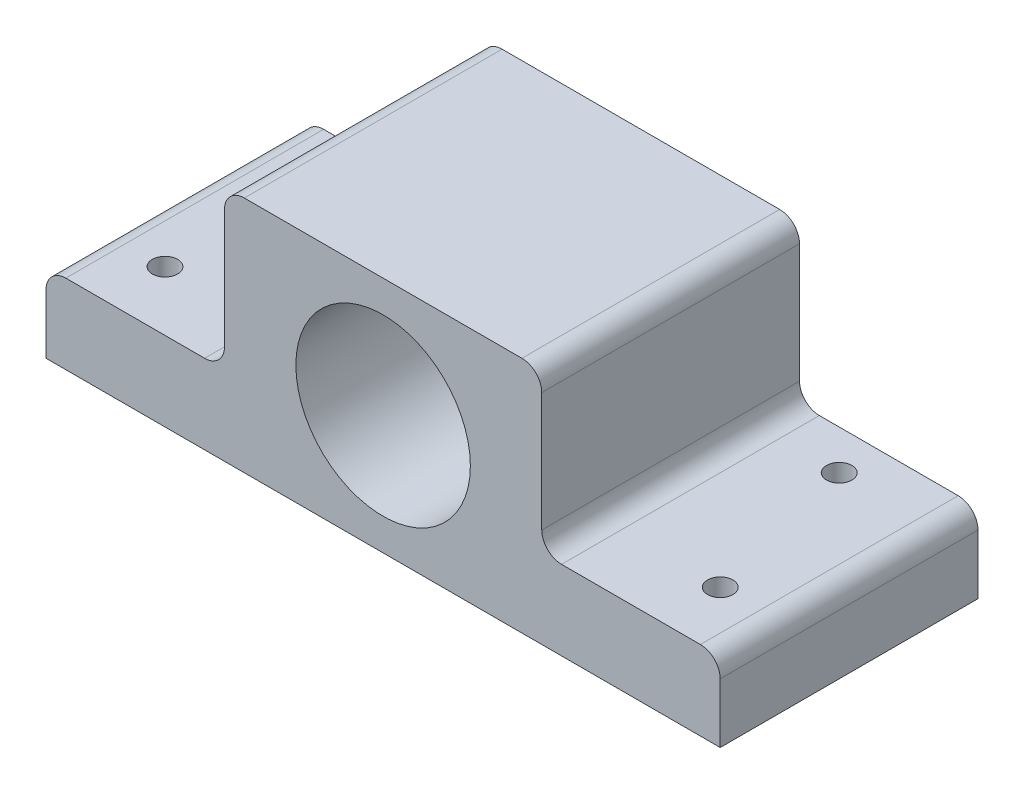
SolidWorks part; units mm, degrees
ref_plane "Front Plane" through (0, 0, 0) normal (0, 0, 1) x (1, 0, 0)
ref_plane "Top Plane" through (0, 0, 0) normal (0, 1, 0) x (1, 0, 0)
ref_plane "Right Plane" through (0, 0, 0) normal (1, 0, 0) x (0, 0, -1)
sketch "Sketch2" plane through (0, 0, 0) normal (0, 0, 1) x (1, 0, 0)
  line L0 (0, 30) -> (85, 0) construction
  line L1 (0, 0) -> (85, 0)
  line L2 (0, 0) -> (0, 30)
  line L3 (0, 30) -> (85, 30)
  line L4 (85, 0) -> (85, 30)
  line L5 (42.5, 30) -> (42.5, 15) construction
  line L6 (62.5, 30) -> (85, 30)
  line L7 (62.5, 30) -> (62.5, 10)
  line L8 (62.5, 10) -> (85, 10)
  line L9 (85, 30) -> (85, 10)
  line L10 (22.5, 10) -> (0, 10)
  line L11 (22.5, 30) -> (22.5, 10)
  circle A0 centre (42.5, 15) radius 11
  point P17 (35.6369, -34.9312)
  dimension "D3" = 22
  dimension "D1" = 30
  dimension "D2" = 85
  dimension "D4" = 20
  dimension "D5" = 22.5
extrude "Boss-Extrude1" add sketch "Sketch2" along normal blind 15 and the other way blind 17.5 contours L3 L11 L10 L2 L1 L4 L8 L7 A0 region at (0.9014, 5, 0)
sketch "Sketch3" plane through (0, 0, 0) normal (0, 1, 0) x (1, 0, 0)
  line L0 (0, -7.5) -> (85, -7.5) construction
  line L3 (42.5, 17.5) -> (42.5, -15) construction
  line L10 (0, 17.5) -> (0, -15) construction
  line L11 (85, 17.5) -> (85, -15) construction
  line L12 (22.5, -15) -> (62.5, -15) construction
  circle A0 centre (7.5, -7.5) radius 1.6
  circle A1 centre (77.5, -7.5) radius 1.6
  circle A2 centre (72.5, 12.5) radius 1.6
  circle A3 centre (12.5, 12.5) radius 1.6
  point P6 (0, 0)
  point P7 (0, 0)
  point P8 (0, 0)
  point P9 (0, 0)
  point P15 (0, 0)
  point P17 (0, 0)
  point P22 (0, 0)
  point P23 (0, 0)
  point P24 (0, 0)
  point P29 (0, 0)
  dimension "D1" = 3.2
  dimension "D3" = 3.2
  dimension "D4" = 20
  dimension "D6" = 7.5
  dimension "D2" = 70
  dimension "D5" = 30
extrude "Cut-Extrude1" cut sketch "Sketch3" along normal through all both and the other way through all contours A2 | A3 | A0 | A1 region at (7.5, 0, 7.5) region at (77.5, 0, 7.5) region at (72.5, 0, -12.5) region at (12.5, 0, -12.5)
fillet "Fillet1" radius 2.5 6 edges at (62.5, 10, -1.25) (22.5, 10, -1.25) (85, 10, -1.25) (0, 10, -1.25) (62.5, 30, -1.25) (22.5, 30, -1.25)
